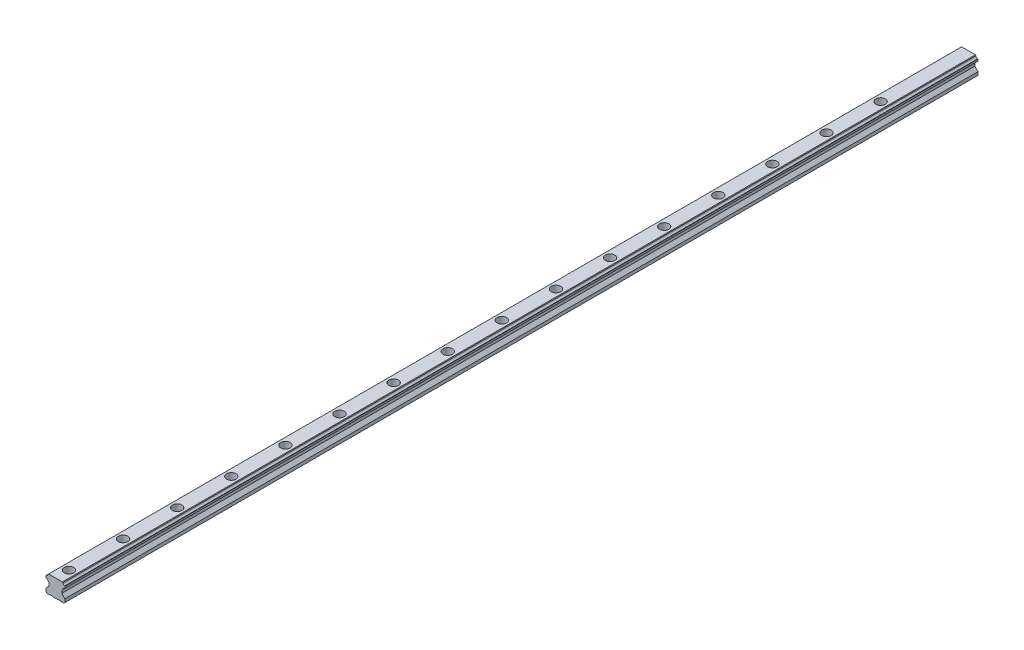
SolidWorks part; units mm, degrees
material "Plain Carbon Steel"
ref_plane "Front Plane" through (0, 0, 0) normal (0, 0, 1) x (1, 0, 0)
ref_plane "Top Plane" through (0, 0, 0) normal (0, 1, 0) x (1, 0, 0)
ref_plane "Right Plane" through (0, 0, 0) normal (1, 0, 0) x (0, 0, -1)
sketch "Sketch1" plane through (-20, 0, 0) normal (0, 0, 1) x (1, 0, 0)
  line L0 (6, 22.215) -> (6, 19.7791)
  line L1 (6, 19.7791) -> (6.4691, 19.31)
  line L2 (9.0004, 16.7787) -> (10.6997, 15.0794)
  line L3 (10.6997, 15.0794) -> (10.6997, 10.9996)
  line L4 (10.6997, 10.9996) -> (6, 6.3)
  line L5 (6, 6.3) -> (6, 1.5)
  line L6 (6, 1.5) -> (7.5, 0)
  line L7 (7.5, 0) -> (12.25, 0)
  line L8 (12.25, 0) -> (12.75, 0.5)
  line L9 (12.75, 0.5) -> (16.25, 0.5)
  line L10 (16.25, 0.5) -> (16.75, 0)
  line L11 (16.75, 0) -> (23.25, 0)
  line L12 (20, 26) -> (20, 0) construction
  line L13 (33.5309, 22.6905) -> (34, 22.215)
  line L14 (30.2142, 26) -> (30.9996, 25.2147)
  line L15 (23.75, 0.5) -> (23.25, 0)
  line L16 (27.25, 0.5) -> (23.75, 0.5)
  line L17 (27.75, 0) -> (27.25, 0.5)
  line L18 (32.5, 0) -> (27.75, 0)
  line L19 (34, 1.5) -> (32.5, 0)
  line L20 (34, 6.3) -> (34, 1.5)
  line L21 (29.3003, 10.9996) -> (34, 6.3)
  line L22 (29.3003, 15.0794) -> (29.3003, 10.9996)
  line L23 (30.9996, 16.7787) -> (29.3003, 15.0794)
  line L24 (34, 19.7791) -> (33.5309, 19.31)
  line L25 (30.2142, 26) -> (9.7858, 26)
  line L26 (9.7858, 26) -> (9.0004, 25.2147)
  line L27 (6.4691, 22.6905) -> (6, 22.215)
  line L28 (34, 22.215) -> (34, 19.7791)
  arc A0 (6.4691, 19.31) -> (9.0004, 16.7787) centre (6.1304, 16.4399) cw
  arc A1 (30.9996, 25.2147) -> (33.5309, 22.6905) centre (33.8688, 25.5607) ccw
  arc A2 (33.5309, 19.31) -> (30.9996, 16.7787) centre (33.8696, 16.4399) ccw
  arc A3 (9.0004, 25.2147) -> (6.4691, 22.6905) centre (6.1312, 25.5607) cw
  dimension "D19" = 2.89
  dimension "D24" = 3.3095
  dimension "D1" = 26
  dimension "D2" = 28
  dimension "D3" = 6.5
  dimension "D4" = 0.5
  dimension "D5" = 3.5
  dimension "D6" = 0.5
  dimension "D7" = 0.5
  dimension "D8" = 1.5
  dimension "D9" = 1.5
  dimension "D10" = 4.8
  dimension "D11" = 4.6996
  dimension "D12" = 4.6997
  dimension "D13" = 4.0798
  dimension "D14" = 1.6993
  dimension "D15" = 1.6993
  dimension "D16" = 20.4285
  dimension "D17" = 0.7853
  dimension "D18" = 0.4691
  dimension "D20" = 0.7853
  dimension "D21" = 0.4755
  dimension "D22" = 2.4359
  dimension "D23" = 0.4691
extrude "Extrude1" add sketch "Sketch1" against normal blind 1350
sketch "Sketch2" plane through (0, 0, 0) normal (1, 0, 0) x (0, 0, -1)
  line L0 (20, 26) -> (27, 26)
  line L1 (27, 26) -> (27, 14)
  line L2 (27, 14) -> (24.5, 14)
  line L3 (24.5, 14) -> (24.5, 0)
  line L4 (24.5, 0) -> (20, 0)
  line L5 (20, 0) -> (20, 26) construction
  line L6 (20, 0) -> (20, 26) construction
  line L7 (20, 26) -> (20, 0)
  line L8 (1350, 0) -> (0, 0) construction
  line L9 (1350, 26) -> (0, 26) construction
  dimension "D1" = 14
  dimension "D2" = 9
  dimension "D3" = 12
  dimension "D4" = 20
revolve "Cut-Revolve1" cut sketch "Sketch2" angle 360 about L6 reverse direction yes
ref_axis "Axis1" through (0, 0, -294) along (0, 0, 1)
pattern_linear "LPattern1" count 16 spacing 80 along (0, 0, -1) of "Cut-Revolve1"
